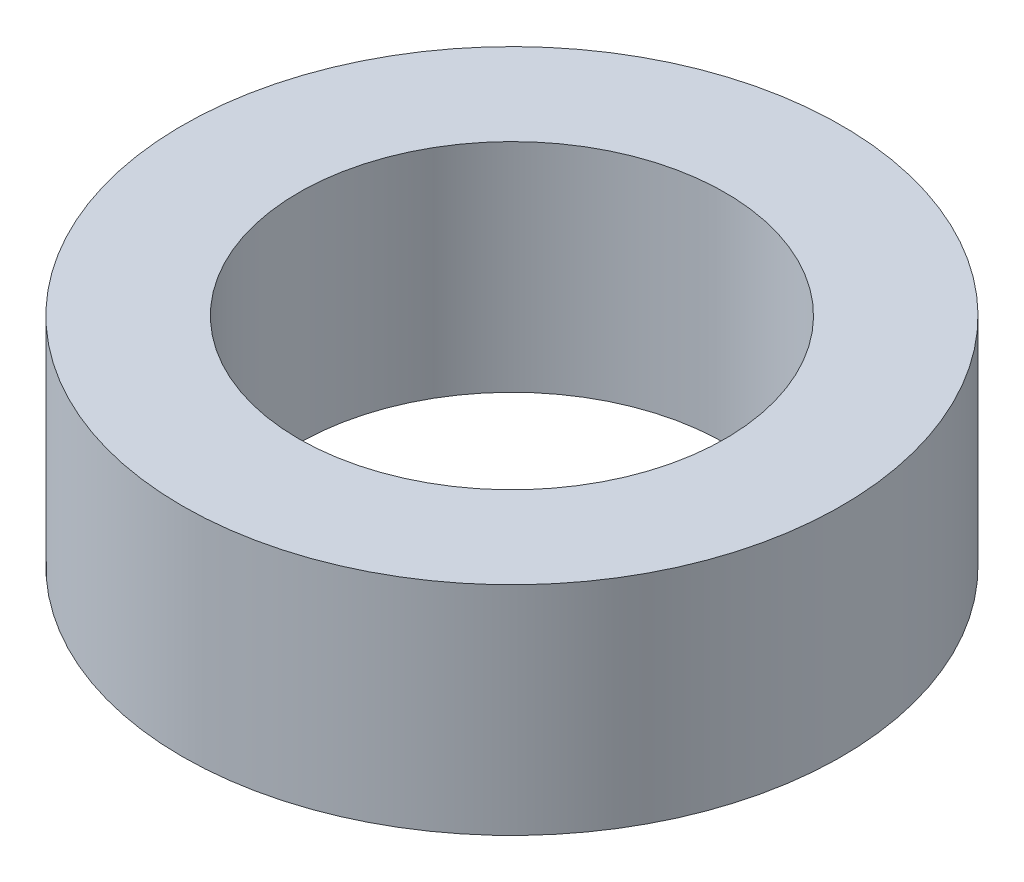
SolidWorks part; units mm, degrees
ref_plane "Front Plane" through (0, 0, 0) normal (0, 0, 1) x (1, 0, 0)
ref_plane "Top Plane" through (0, 0, 0) normal (0, 1, 0) x (1, 0, 0)
ref_plane "Right Plane" through (0, 0, 0) normal (1, 0, 0) x (0, 0, -1)
sketch "Sketch1" plane through (0, 0, 0) normal (0, 1, 0) x (1, 0, 0)
  circle A0 centre (0, 0) radius 42.5
  dimension "FLANGE_OD" = 85
extrude "Boss-Extrude1" add sketch "Sketch1" along normal blind 28
sketch "Sketch2" plane through (0, 0, 0) normal (0, 1, 0) x (1, 0, 0)
  circle A0 centre (0, 0) radius 27.5
  dimension "BORE_D" = 55
extrude "Cut-Extrude1" cut sketch "Sketch2" along normal through all
sketch "Sketch3" plane through (0, 28, 0) normal (0, 1, 0) x (1, 0, 0)
  circle A0 centre (0, 0) radius 19.4406 construction
  circle A1 centre (-19.4406, 0) radius 1.6312
  dimension "BOLT_D" = 3.2625
  dimension "BOLT_PCD" = 38.8813
extrude "Cut-Extrude2" cut sketch "Sketch3" against normal blind 21.1404 rebuild error yes
pattern_circular "CirPattern1" count 6 over 360 rebuild error yes
